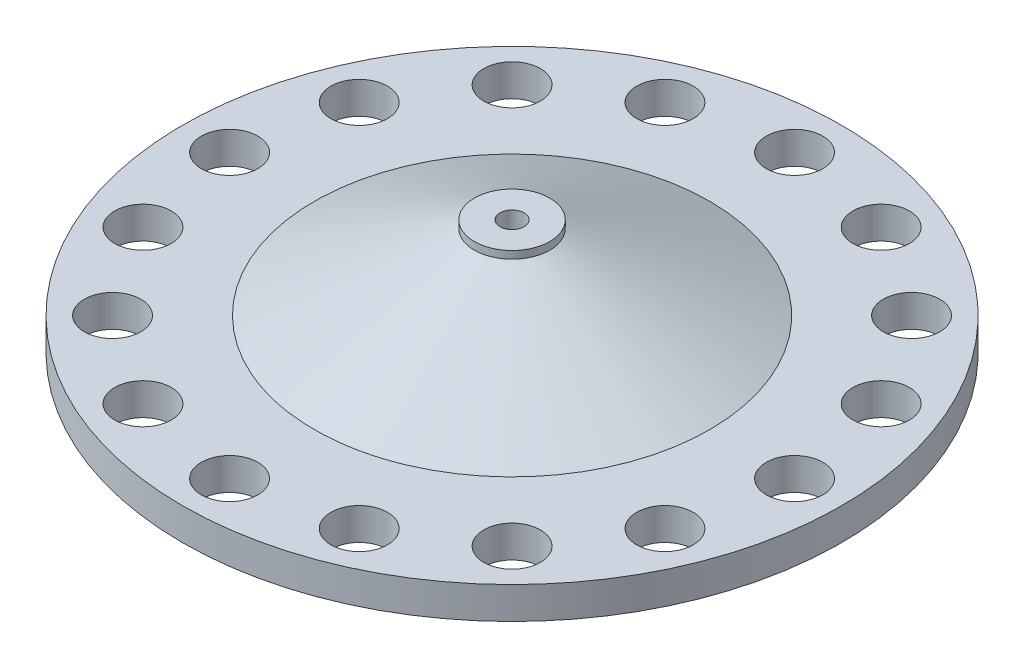
SolidWorks part; units mm, degrees
ref_plane "Front Plane" through (0, 0, 0) normal (0, 0, 1) x (1, 0, 0)
ref_plane "Top Plane" through (0, 0, 0) normal (0, 1, 0) x (1, 0, 0)
ref_plane "Right Plane" through (0, 0, 0) normal (1, 0, 0) x (0, 0, -1)
sketch "Sketch2" plane through (0, 0, 0) normal (0, 1, 0) x (1, 0, 0)
  circle A0 centre (0, 0) radius 175
extrude "Boss-Extrude1" add sketch "Sketch2" along normal blind 17
sketch "Sketch3" plane through (0, 17, 0) normal (0, 1, 0) x (1, 0, 0)
  circle A0 centre (0, 0) radius 105
ref_plane "Plane1" through (0, 57, 0) normal (0, 1, 0) x (1, 0, 0)
sketch "Sketch4" plane through (0, 57, 0) normal (0, 1, 0) x (1, 0, 0)
  circle A0 centre (0, 0) radius 20
loft "Loft1" add profiles "Sketch4", "Sketch3" connector at (4.6423, 57, -19.4538) connector at (0.6597, 17, -104.9979)
sketch "Sketch5" plane through (0, 17, 0) normal (0, 1, 0) x (1, 0, 0)
  circle A3 centre (-150, 0) radius 15
  circle A4 centre (-138.5819, 57.4025) radius 15
  circle A5 centre (-106.066, 106.066) radius 15
  circle A6 centre (-57.4025, 138.5819) radius 15
  circle A7 centre (0, 150) radius 15
  circle A8 centre (57.4025, 138.5819) radius 15
  circle A9 centre (106.066, 106.066) radius 15
  circle A10 centre (138.5819, 57.4025) radius 15
  circle A11 centre (150, 0) radius 15
  circle A12 centre (138.5819, -57.4025) radius 15
  circle A13 centre (106.066, -106.066) radius 15
  circle A14 centre (57.4025, -138.5819) radius 15
  circle A15 centre (0, -150) radius 15
  circle A16 centre (-57.4025, -138.5819) radius 15
  circle A17 centre (-106.066, -106.066) radius 15
  circle A18 centre (-138.5819, -57.4025) radius 15
  dimension "D1" = 16
extrude "Cut-Extrude1" cut sketch "Sketch5" against normal blind 17
sketch "Sketch6" plane through (0, 57, 0) normal (0, 1, 0) x (1, 0, 0)
  circle A0 centre (0, 0) radius 20
extrude "Boss-Extrude2" add sketch "Sketch6" along normal blind 4
sketch "Sketch7" plane through (0, 61, 0) normal (0, 1, 0) x (1, 0, 0)
  circle A0 centre (0, 0) radius 6.4
  dimension "D1" = 12.8
extrude "Cut-Extrude2" cut sketch "Sketch7" against normal through all
